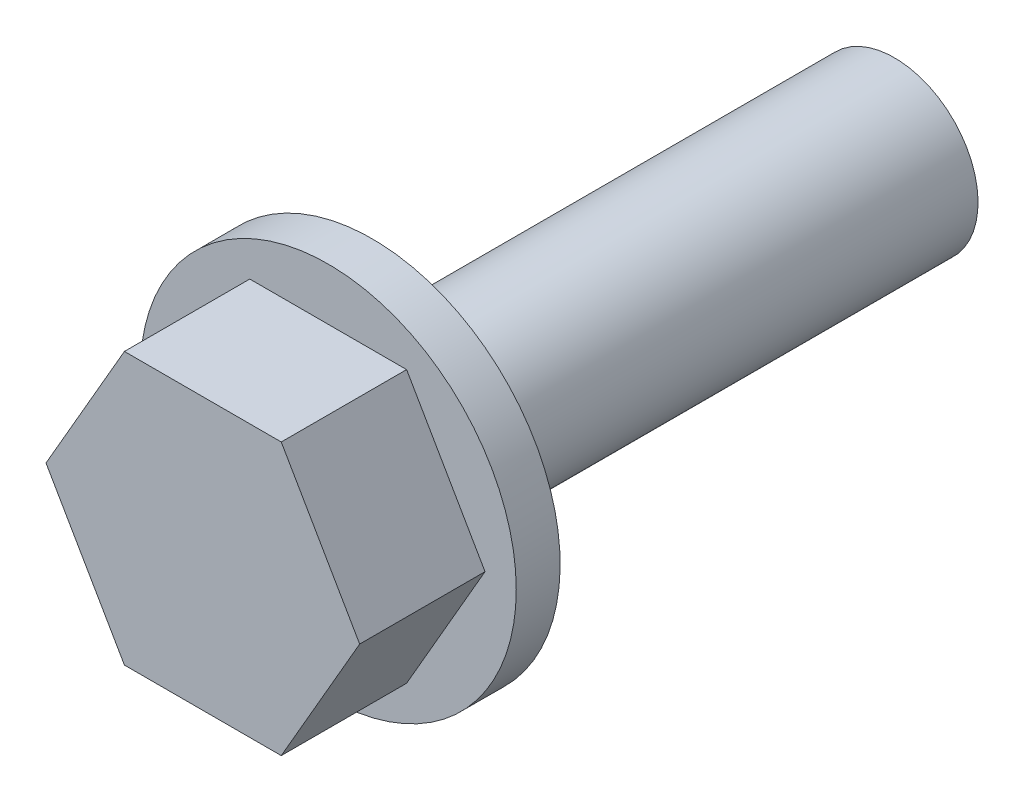
SolidWorks part; units mm, degrees
material "Alloy Steel"
ref_plane "Front Plane" through (0, 0, 0) normal (0, 0, 1) x (1, 0, 0)
ref_plane "Top Plane" through (0, 0, 0) normal (0, 1, 0) x (1, 0, 0)
ref_plane "Right Plane" through (0, 0, 0) normal (1, 0, 0) x (0, 0, -1)
ref_axis "Axis1" through (0, 0, -52.8182) along (0, 0, 1)
ref_axis "Axis2" through (0, -15.5981, 0) along (0, 1, 0)
ref_axis "Axis3" through (-12.2581, 0, 0) along (1, 0, 0)
sketch "Sketch1" plane through (0, 0, 0) normal (1, 0, 0) x (0, 0, -1)
  line L0 (-8.1, 0) -> (-8.1, 9)
  line L1 (-8.1, 9) -> (0, 9)
  line L2 (0, 9) -> (0, 4)
  line L3 (0, 4) -> (25, 4)
  line L4 (25, 4) -> (25, 0)
  line L5 (25, 0) -> (-8.1, 0)
  line L6 (-5.5849, 0) -> (13.8966, 0) construction
  dimension "D1" = 8
  dimension "D2" = 18
  dimension "D3" = 8.1
  dimension "Length" = 25
revolve "Revolve1" add sketch "Sketch1" angle 360 about L6
cosmetic thread "Cosmetic Thread1" parameters "D1"=25, "D2"=6.619
sketch "Sketch2" plane through (0, 0, 8.1) normal (0, 0, 1) x (1, 0, 0)
  line L1 (3.7528, -6.5) -> (7.5056, 0)
  line L2 (7.5056, 0) -> (3.7528, 6.5)
  line L3 (3.7528, 6.5) -> (-3.7528, 6.5)
  line L4 (-3.7528, 6.5) -> (-7.5056, 0)
  line L5 (-7.5056, 0) -> (-3.7528, -6.5)
  line L6 (-3.7528, -6.5) -> (3.7528, -6.5)
  circle A0 centre (0, 0) radius 6.5 construction
  dimension "D1" = 13
extrude "Cut-Extrude1" cut sketch "Sketch2" against normal blind 6 flip side to cut
